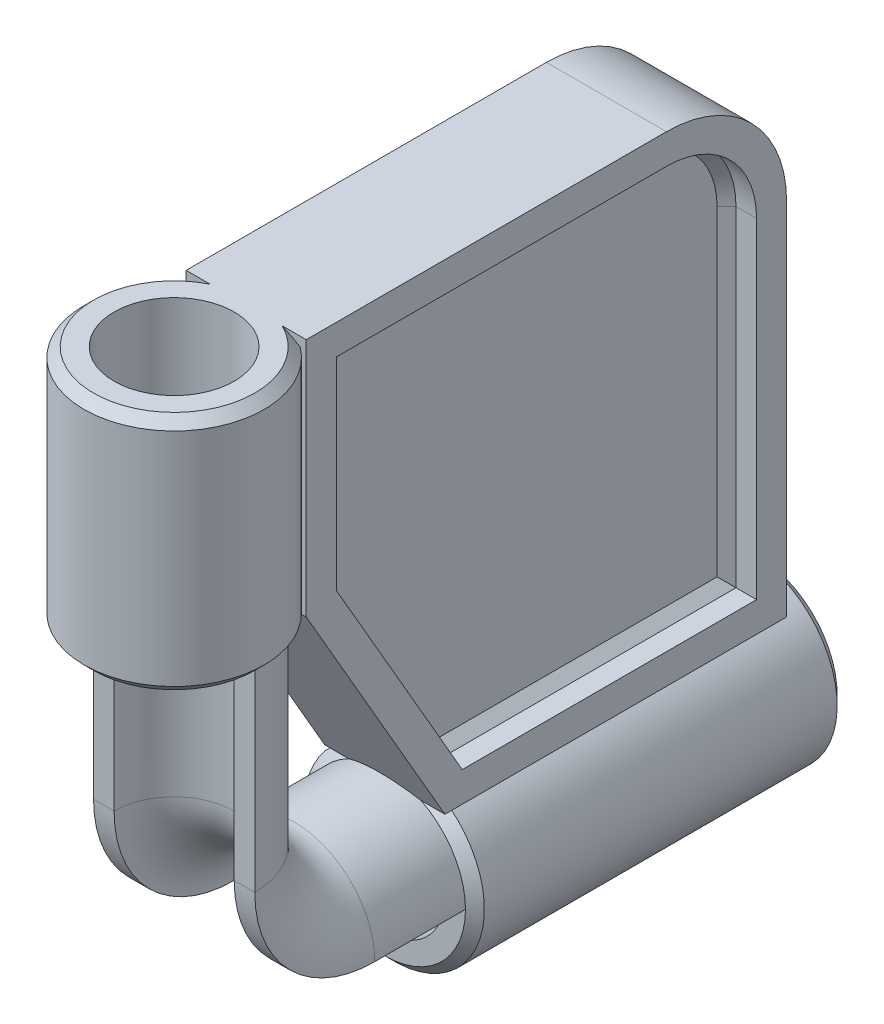
SolidWorks part; units mm, degrees
ref_plane "Front Plane" through (0, 0, 0) normal (1, 0, 0) x (0, 1, 0)
ref_plane "Top Plane" through (0, 0, 0) normal (0, 0, 1) x (0, 1, 0)
ref_plane "Right Plane" through (0, 0, 0) normal (0, 1, 0) x (-1, 0, 0)
sketch "Sketch1" plane through (0, 0, 0) normal (1, 0, 0) x (0, 1, 0)
  line L0 (-25.4, 10.7353) -> (0, 25.4)
  line L1 (-25.4, -25.4) -> (25.4, -25.4)
  line L2 (-25.4, -25.4) -> (-25.4, 10.7353)
  line L3 (0, 25.4) -> (25.4, 25.4)
  line L4 (25.4, -25.4) -> (25.4, 25.4)
  line L5 (0, -55) -> (0, 55) construction
  line L6 (55, 0) -> (-55, 0) construction
  point P0 (0, 0)
  point P10 (25.4, 0)
  dimension "D1" = 50.8
  dimension "D2" = 50.8
  dimension "D3" = 30
  dimension "D4" = 25.4
extrude "Boss-Extrude1" add sketch "Sketch1" along normal mid plane 12.7
fillet "Fillet1" radius 12.7 1 edges at (0, 25.4, -25.4)
sketch "Sketch3" plane through (6.35, 0, 0) normal (1, 0, 0) x (0, 1, 0)
  line L10 (-22.225, -22.225) -> (12.7, -22.225)
  line L11 (22.225, -12.7) -> (22.225, 22.225)
  line L12 (22.225, 22.225) -> (0.8507, 22.225)
  line L13 (0.8507, 22.225) -> (-22.225, 8.9022)
  line L14 (-22.225, 8.9022) -> (-22.225, -22.225)
  line L15 (-22.225, -22.225) -> (12.7, -22.225)
  line L16 (22.225, -12.7) -> (22.225, 22.225)
  line L17 (22.225, 22.225) -> (0.8507, 22.225)
  line L18 (0.8507, 22.225) -> (-22.225, 8.9022)
  line L19 (-22.225, 8.9022) -> (-22.225, -22.225)
  arc A2 (12.7, -22.225) -> (22.225, -12.7) centre (12.7, -12.7) ccw
  arc A3 (12.7, -22.225) -> (22.225, -12.7) centre (12.7, -12.7) ccw
  dimension "D1" = 3.175
extrude "Cut-Extrude2" cut sketch "Sketch3" against normal blind 3.175
sketch "Sketch4" plane through (0, 0, -25.4) normal (0, 0, -1) x (1, 0, 0)
  line L0 (0, -37.3697) -> (0, 37.3697) construction
  line L1 (6.35, -25.4) -> (-6.35, -25.4) construction
  circle A0 centre (0, 33.02) radius 9.525
  circle A1 centre (0, 33.02) radius 6.35
  dimension "D1" = 19.05
  dimension "D2" = 12.7
  dimension "D3" = 58.42
extrude "Boss-Extrude2" add sketch "Sketch4" against normal up to vertex (36.1353 mm away) and the other way blind 3.175 up to point (6.35, -25.4, 10.7353)
sketch "Sketch5" plane through (0, 25.4, 0) normal (0, 1, 0) x (-1, 0, 0)
  line L0 (0, 37.3697) -> (0, -37.3697) construction
  line L1 (-5.715, -25.4) -> (5.715, -25.4) construction
  circle A0 centre (0, 33.02) radius 9.525
  circle A1 centre (0, 33.02) radius 6.35
  dimension "D1" = 19.05
  dimension "D2" = 12.7
  dimension "D3" = 58.42
extrude "Boss-Extrude3" add sketch "Sketch5" against normal up to surface (25.4 mm away) up to plane "Right Plane"
chamfer "Chamfer2" distance 1 angle 45 4 edges at (0, 0, 42.545) (0, -42.545, 10.7353) (0, -23.495, -28.575) (0, 25.4, 42.545)
sketch "Sketch6" plane through (0, 0, 0) normal (1, 0, 0) x (0, 1, 0)
  line L0 (-26.67, 10.7353) -> (-39.37, 10.7353) construction
  line L1 (-26.67, 10.7353) -> (-39.37, 10.7353) construction
  line L2 (0, 39.37) -> (0, 26.67) construction
  line L3 (0, 39.37) -> (0, 26.67) construction
  line L4 (-20.32, 33.02) -> (0, 33.02)
  line L5 (-33.02, 20.32) -> (-33.02, 10.7353)
  arc A0 (-33.02, 20.32) -> (-20.32, 33.02) centre (-20.32, 20.32) cw
  point P6 (-33.02, 10.7353)
  point P9 (0, 33.02)
  dimension "D1" = 12.7
sketch "Sketch7" plane through (0, 0, 0) normal (0, -1, 0) x (1, 0, 0)
  line L0 (-8.525, 33.02) -> (-6.35, 33.02)
  line L1 (6.35, 33.02) -> (8.525, 33.02)
  line L2 (0, 39.37) -> (0, 26.67) construction
  circle A0 centre (0, 33.02) radius 6.35 construction
  arc A4 (-6.35, 33.02) -> (6.35, 33.02) centre (0, 33.02) ccw
  arc A5 (-8.525, 33.02) -> (8.525, 33.02) centre (0, 33.02) ccw
  arc A6 (3.8225, 25.4) -> (-3.8225, 25.4) centre (0, 33.02) ccw construction
sweep "Sweep3" add profiles "Sketch7" path "Sketch6"
chamfer "Chamfer4" distance 1 angle 45 6 edges at (3.175, -10.6871, 15.5636) (3.175, 11.5379, 22.225) (3.175, 22.225, 4.7625) (3.175, 19.4352, -19.4352) (3.175, -4.7625, -22.225) (3.175, -22.225, -6.6614)
